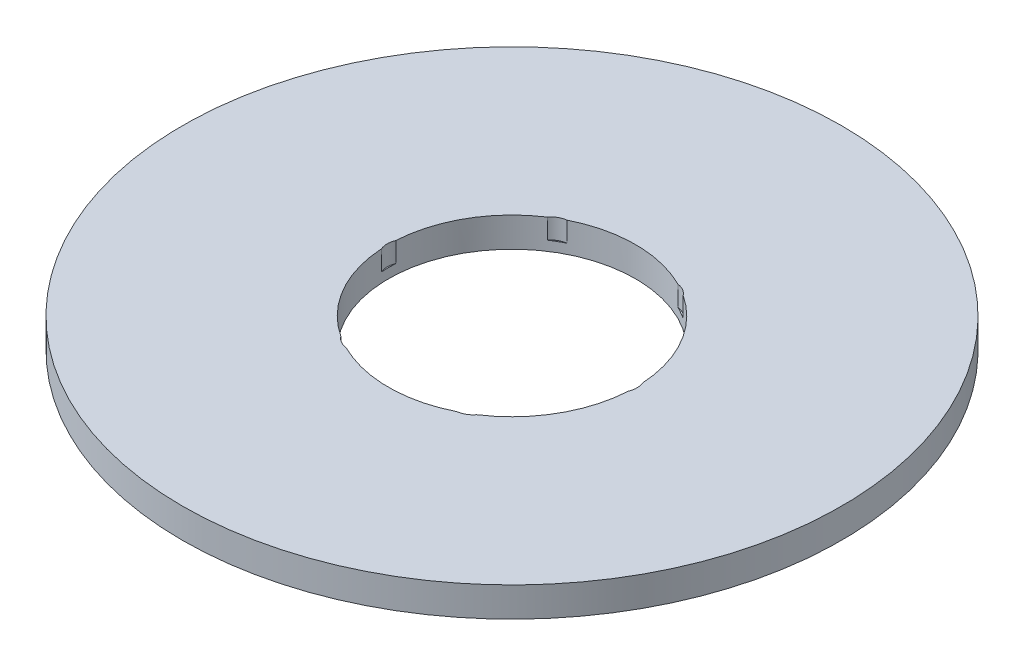
SolidWorks part; units mm, degrees
ref_plane "Front Plane" through (0, 0, 0) normal (0, 0, 1) x (1, 0, 0)
ref_plane "Top Plane" through (0, 0, 0) normal (0, 1, 0) x (1, 0, 0)
ref_plane "Right Plane" through (0, 0, 0) normal (1, 0, 0) x (0, 0, -1)
sketch "Sketch1" plane through (0, 0, 0) normal (0, 1, 0) x (1, 0, 0)
  circle A0 centre (0, 0) radius 100
  dimension "FLANGE_OD" = 200
extrude "Boss-Extrude1" add sketch "Sketch1" along normal blind 9
sketch "Sketch2" plane through (0, 0, 0) normal (0, 1, 0) x (1, 0, 0)
  circle A0 centre (0, 0) radius 37.5
  dimension "BORE_D" = 75
extrude "Cut-Extrude1" cut sketch "Sketch2" along normal through all
sketch "Sketch3" plane through (0, 9, 0) normal (0, 1, 0) x (1, 0, 0)
  circle A0 centre (0, 0) radius 32.2064 construction
  circle A1 centre (-32.2064, 0) radius 5.6683
  dimension "BOLT_D" = 11.3366
  dimension "BOLT_PCD" = 64.4128
extrude "Cut-Extrude2" cut sketch "Sketch3" against normal blind 6.0683
pattern_circular "CirPattern1" count 6 over 360 about axis through (0, 0, 0) along (0, 1, 0) of "Cut-Extrude2"
